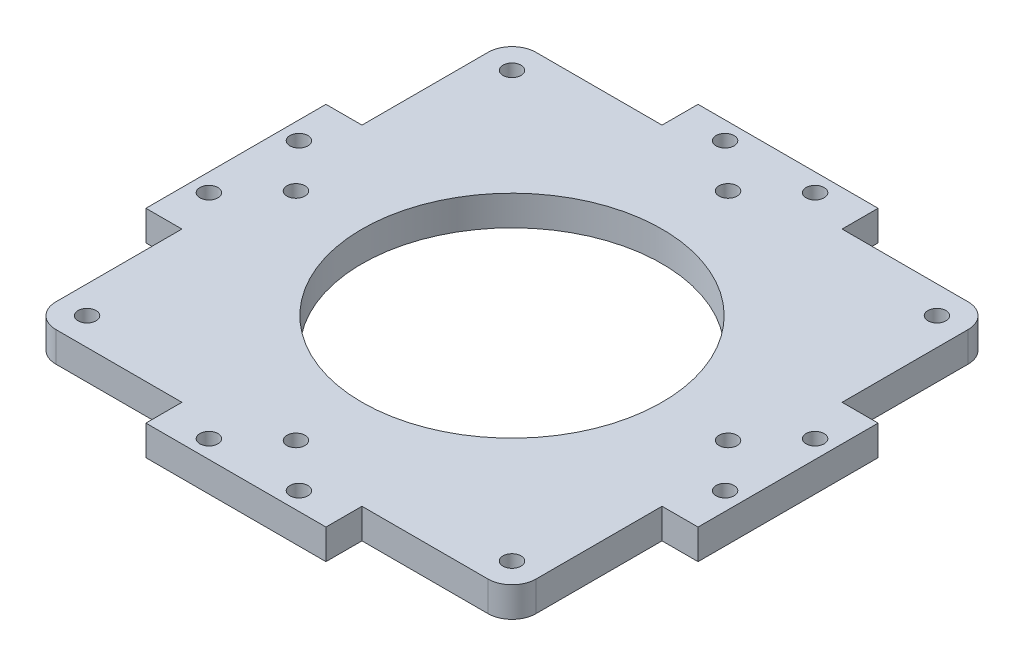
SolidWorks part; units mm, degrees
material "ABS"
ref_plane "前视基准面" through (0, 0, 0) normal (0, 0, 1) x (1, 0, 0)
ref_plane "上视基准面" through (0, 0, 0) normal (0, 1, 0) x (1, 0, 0)
ref_plane "右视基准面" through (0, 0, 0) normal (1, 0, 0) x (0, 0, -1)
ref_axis "基准轴1" through (0, 55, 0) along (0, -1, 0)
sketch "草图1" plane through (0, 0, 0) normal (0, 1, 0) x (1, 0, 0)
  line L1 (-40, 40) -> (40, 40)
  line L2 (-40, 40) -> (-40, -40)
  line L3 (-40, -40) -> (40, -40)
  line L4 (40, 40) -> (40, -40)
  line L5 (-40, 40) -> (40, -40) construction
  line L6 (-40, -40) -> (40, 40) construction
  circle A0 centre (0, 0) radius 25
  point P0 (0, 0)
  dimension "D3" = 50
  dimension "D1" = 80
  dimension "D2" = 80
extrude "凸台-拉伸1" add sketch "草图1" along normal blind 5
sketch "草图3" plane through (0, 0, 0) normal (0, 1, 0) x (1, 0, 0)
  line L0 (-40, 40) -> (40, -40) construction
  line L1 (-40, 40) -> (40, 40) construction
  circle A0 centre (0, 36) radius 1.5
  circle A1 centre (-35.4038, 35.4038) radius 1.5
  dimension "D1" = 3
  dimension "D2" = 3
  dimension "D3" = 4
  dimension "D4" = 6.5
extrude "切除-拉伸2" cut sketch "草图3" along normal blind 5
pattern_circular "阵列(圆周)1" count 4 over 360 about axis through (0, 55, 0) along (0, -1, 0) of "切除-拉伸2"
fillet "圆角1" radius 4 4 edges at (40, 2.5, 40) (40, 2.5, -40) (-40, 2.5, 40) (-40, 2.5, -40)
sketch "草图7" plane through (0, 0, 0) normal (0, 1, 0) x (1, 0, 0)
  line L0 (-15, -40) -> (15, -40)
  line L1 (-36, -40) -> (36, -40) construction
  line L2 (15, -40) -> (15, -46)
  line L3 (15, -46) -> (-15, -46)
  line L4 (-15, -46) -> (-15, -40)
  circle A0 centre (-7.5, -43) radius 1.5
  circle A1 centre (7.5, -43) radius 1.5
  point P5 (0, -40)
  point P10 (0, -43)
  dimension "D5" = 3
  dimension "D6" = 3
  dimension "D1" = 30
  dimension "D2" = 6
  dimension "D3" = 3
  dimension "D4" = 15
extrude "凸台-拉伸2" add sketch "草图7" along normal blind 5
pattern_circular "阵列(圆周)2" count 4 over 360 about axis through (0, 55, 0) along (0, -1, 0) of "凸台-拉伸2"
